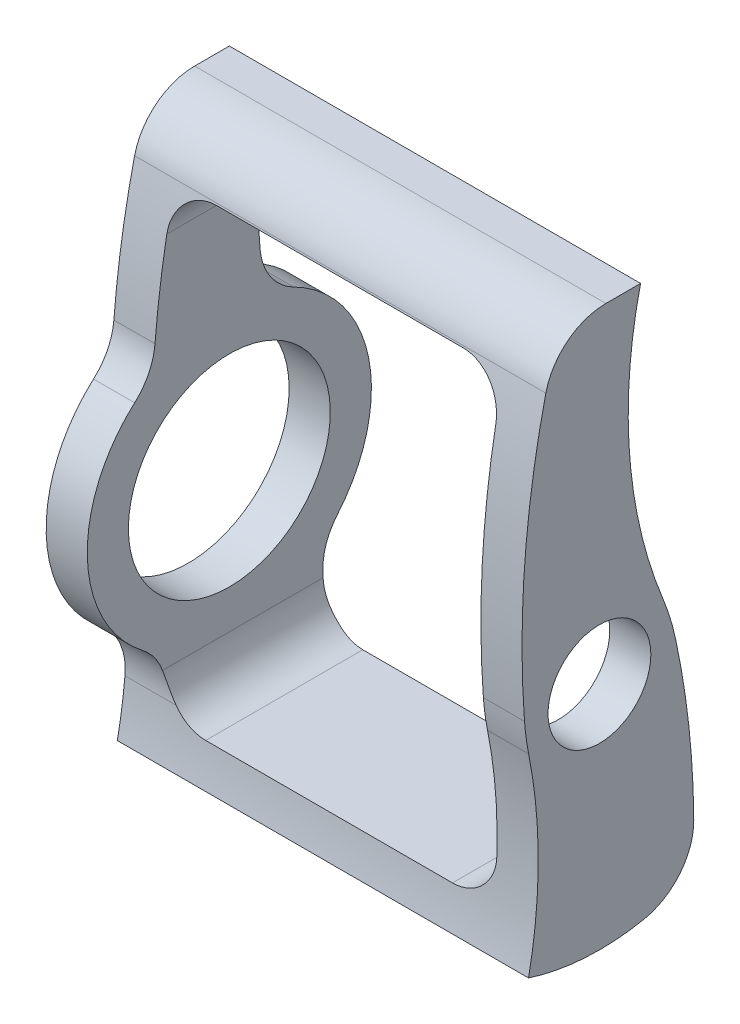
SolidWorks part; units mm, degrees
other "Markup2"
sketch "Sketch9" plane through (31.75, 50.4016, 20.35) normal (0.8402, 0.4575, 0.2911) x (0.3274, 0, -0.9449)
material "AISI 4340 Steel, normalized"
ref_plane "Front Plane" through (0, 0, 0) normal (0, 0, 1) x (1, 0, 0)
ref_plane "Top Plane" through (0, 0, 0) normal (0, 1, 0) x (1, 0, 0)
ref_plane "Right Plane" through (0, 0, 0) normal (1, 0, 0) x (0, 0, -1)
other "Center of Mass"
sketch "Weapon Layout" plane through (0, 0, 0) normal (1, 0, 0) x (0, 0, -1)
  line L0 (-6.35, 50.4016) -> (6.35, 50.4016) construction
  line L1 (-10.9443, -33.834) -> (14.4209, -32.5046) construction
  line L2 (6.35, 50.4016) -> (-5.4537, 0) construction
  line L3 (6.35, 50.4016) -> (0, 0) construction
  line L4 (0, 0) -> (0, -33.2604) construction
  circle A0 centre (0, 0) radius 14 construction
  circle A1 centre (0, 0) radius 50.8 construction
  circle A2 centre (0, 0) radius 17.175 construction
  circle A3 centre (0, 0) radius 20.35 construction
  arc A4 (-6.35, 50.4016) -> (-20.35, 0) centre (77.3756, 0) ccw construction
  arc A5 (23.3803, -26.7932) -> (-23.7089, -26.5029) centre (0, 0) cw construction
  arc A6 (6.35, 50.4016) -> (15.4347, 13.2625) centre (47.4536, 40.7754) ccw construction
  dimension "D1" = 28
  dimension "D2" = 101.6
  dimension "D3" = 3.175
  dimension "D4" = 6.35
  dimension "D5" = 12.7
  dimension "D7" = 6
  dimension "D6" = 15.24
  dimension "D8" = 25.4
  dimension "D9" = 87
sketch "Sketch2" plane through (0, 0, 0) normal (1, 0, 0) x (0, 0, -1)
  line L0 (-6.35, 50.4016) -> (6.35, 50.4016)
  line L1 (-11.3249, -1.5462) -> (0, 0) construction
  line L2 (6.35, 50.4016) -> (-5.4537, 0) construction
  line L3 (-11.5714, 0.7977) -> (-15.24, 50.4016) construction
  arc A0 (-10.9443, -33.834) -> (14.4209, -32.5046) centre (0, 0) ccw
  arc A1 (-23.7089, -26.5029) -> (23.3803, -26.7932) centre (0, 0) ccw construction
  arc A2 (-10.934, -3.8704) -> (-11.5714, 0.7977) centre (26.4248, 3.6078) cw
  arc A3 (9.7952, 6.5275) -> (11.7704, 0.1087) centre (-25.4904, -7.8439) cw
  arc A4 (-11.5714, 0.7977) -> (-6.35, 50.4016) centre (128.3504, 11.1461) cw
  arc A5 (-10.934, -3.8704) -> (-10.9443, -33.834) centre (-85.6518, -18.8267) cw
  arc A6 (6.35, 50.4016) -> (9.7952, 6.5275) centre (76.9323, 33.8717) ccw
  arc A7 (11.7704, 0.1087) -> (14.4209, -32.5046) centre (-112.4323, -26.3999) cw
  circle A9 centre (0, 0) radius 11.43 construction
  point P25 (10.9245, 3.3617)
  dimension "D1" = 127
  dimension "D2" = 38.1
  dimension "D3" = 76.2
  dimension "D4" = 38.1
  dimension "D5" = 22.86
  dimension "D6" = 8.89
extrude "Boss-Extrude2" add sketch "Sketch2" along normal mid plane 63.5
sketch "Sketch3" plane through (0, 0, 0) normal (0, 0, 1) x (1, 0, 0)
  line L0 (31.75, 50.4016) -> (-31.75, 50.4016) construction
  line L1 (-25.4, 42.7816) -> (25.4, 42.7816)
  line L2 (-25.4, 42.7816) -> (-25.4, -27.94)
  line L3 (-25.4, -27.94) -> (25.4, -27.94)
  line L4 (25.4, 42.7816) -> (25.4, -27.94)
  line L6 (-31.75, -35.56) -> (31.75, -35.56) construction
  line L7 (-31.75, 50.4016) -> (-31.75, 0.7977) construction
  dimension "D1" = 7.62
  dimension "D3" = 6.35
  dimension "D4" = 7.62
  dimension "D2" = 6.35
extrude "Cut-Extrude1" cut sketch "Sketch3" against normal through all both and the other way through all
fillet "Fillet1" radius 6.35 4 edges at (-25.4, 42.7816, 1.6753) (25.4, 42.7816, 1.6753) (25.4, -27.94, -2.2798) (-25.4, -27.94, -2.2798)
fillet "Fillet3" radius 9.525 2 edges at (0, -32.5046, -14.4209) (0, 50.4016, 6.35)
sketch "Sketch5" plane through (31.75, 0, 0) normal (1, 0, 0) x (0, 0, -1)
  circle A0 centre (0, 0) radius 7.9375
  circle A1 centre (0, 0) radius 6.35 construction
  dimension "D1" = 12.7
  dimension "D2" = 1.5875
extrude "Cut-Extrude2" cut sketch "Sketch5" against normal up to next
sketch "Sketch6" plane through (-31.75, 0, 0) normal (-1, 0, 0) x (0, 0, 1)
  circle A0 centre (0, 0) radius 21.9375
  circle A1 centre (0, 0) radius 7.9375 construction
  dimension "D1" = 43.875
extrude "Boss-Extrude3" add sketch "Sketch6" against normal up to surface (6.35 mm away) up to face at (-25.4, 4.1451, 0.3502)
fillet "Fillet2" radius 9.525 4 edges at (-28.575, 18.5193, 11.7597) (-28.575, -19.794, 9.458) (-28.575, -16.7229, -14.1985) (-28.575, 21.2233, -5.5522)
sketch "Sketch7" plane through (-31.75, 0, 0) normal (-1, 0, 0) x (0, 0, 1)
  circle A0 centre (0, 0) radius 15.5875
  arc A2 (13.424, -17.3508) -> (14.6231, 16.353) centre (0, 0) ccw construction
  dimension "D1" = 31.175
extrude "Cut-Extrude3" cut sketch "Sketch7" against normal up to next
equation "\"D1@Weapon Layout\" = 28mm"
equation "\"D1@Sketch6\"=28mm+1/2in+1/8in"
equation "\"D1@Sketch7\"=28mm +1/8"
equation "\"D2@Sketch3\"=\"D3@Sketch3\""
